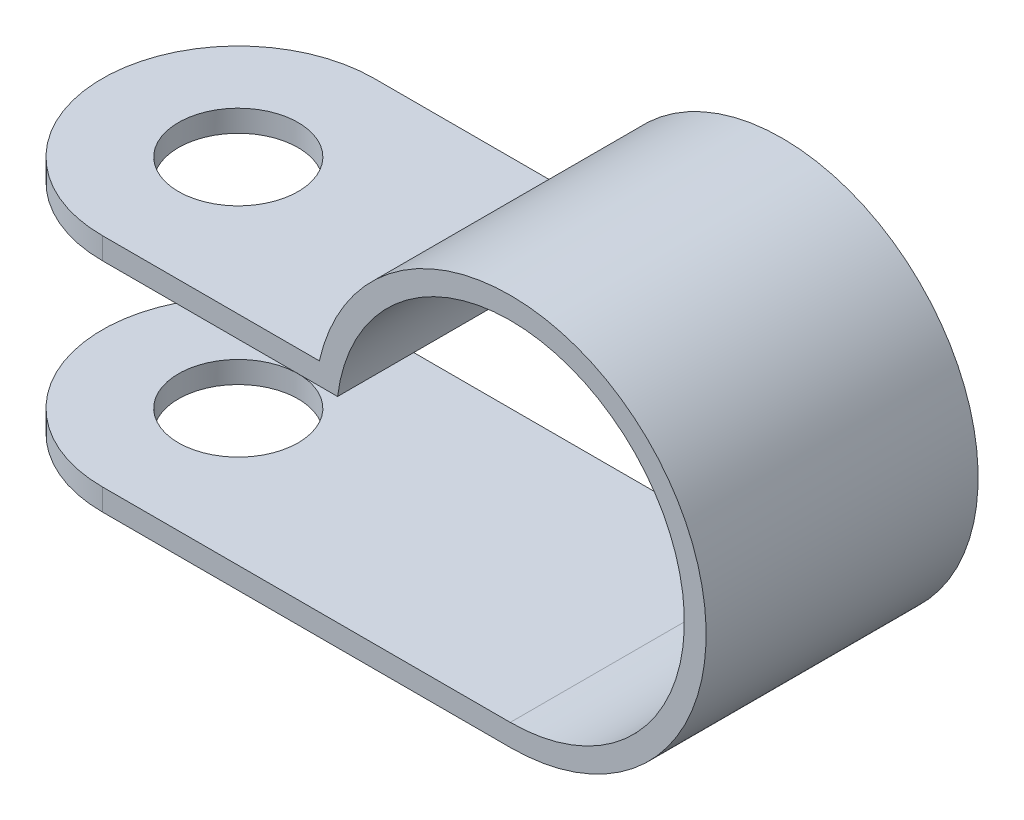
SolidWorks part; units mm, degrees
ref_plane "Front Plane" through (0, 0, 0) normal (0, 0, 1) x (1, 0, 0)
ref_plane "Top Plane" through (0, 0, 0) normal (0, 1, 0) x (1, 0, 0)
ref_plane "Right Plane" through (0, 0, 0) normal (1, 0, 0) x (0, 0, -1)
sketch "Sketch1" plane through (0, 0, 0) normal (0, 0, 1) x (1, 0, 0)
  line L0 (0, 8.382) -> (12.3635, 8.382)
  line L1 (19.05, 0) -> (0, 0)
  line L2 (0, 0) -> (0, 0.762)
  line L3 (0, 0.762) -> (19.05, 0.762)
  line L4 (0, 8.382) -> (0, 7.62)
  line L5 (0, 7.62) -> (13.0018, 7.62)
  arc A0 (12.3635, 8.382) -> (19.05, 0) centre (19.05, 6.858) cw
  arc A1 (13.0018, 7.62) -> (19.05, 0.762) centre (19.05, 6.858) cw
  point P11 (0, 0)
  point P12 (0, 0)
  dimension "D3" = 6.858
  dimension "D1" = 0.762
  dimension "D2" = 0.762
  dimension "D4" = 6.858
  dimension "D5" = 19.05
extrude "Boss-Extrude1" add sketch "Sketch1" along normal blind 9.525
sketch "Sketch2" plane through (0, 8.382, 0) normal (0, 1, 0) x (1, 0, 0)
  line L0 (12.3635, -9.525) -> (0, -9.525) construction
  line L1 (12.3635, 0) -> (0, 0) construction
  line L2 (0, -9.525) -> (0, 0) construction
  line L3 (4.7625, -9.525) -> (0, -9.525)
  line L4 (0, -9.525) -> (0, 0)
  line L5 (0, 0) -> (4.7625, 0)
  arc A0 (4.7625, -9.525) -> (4.7625, 0) centre (4.7625, -4.7625) cw
  circle A1 centre (4.7625, -4.7625) radius 2.0955
  line M1 (12.3635, 0) -> (0, 0)
  line M2 (0, 0) -> (0, -9.525)
  line M3 (0, -9.525) -> (12.3635, -9.525)
  dimension "D1" = 4.191
extrude "Cut-Extrude1" cut sketch "Sketch2" against normal through all contours A1 | A0 M2 M1 | A0 L4 M3 region at (1.0638, 8.382, 1.0638) region at (1.0638, 8.382, 8.4612) region at (4.7625, 8.382, 4.7625)
ref_plane "Plane1" through (0, 0, 4.7625) normal (0, 0, -1) x (-1, 0, 0)
ref_plane "Plane2" through (12.3635, 0, 0) normal (1, 0, 0) x (0, 0, -1)
equation "\"D2@Sketch1\"=\"D1@Sketch1\""
equation "\"D3@Sketch1\"=0.54in/2"
